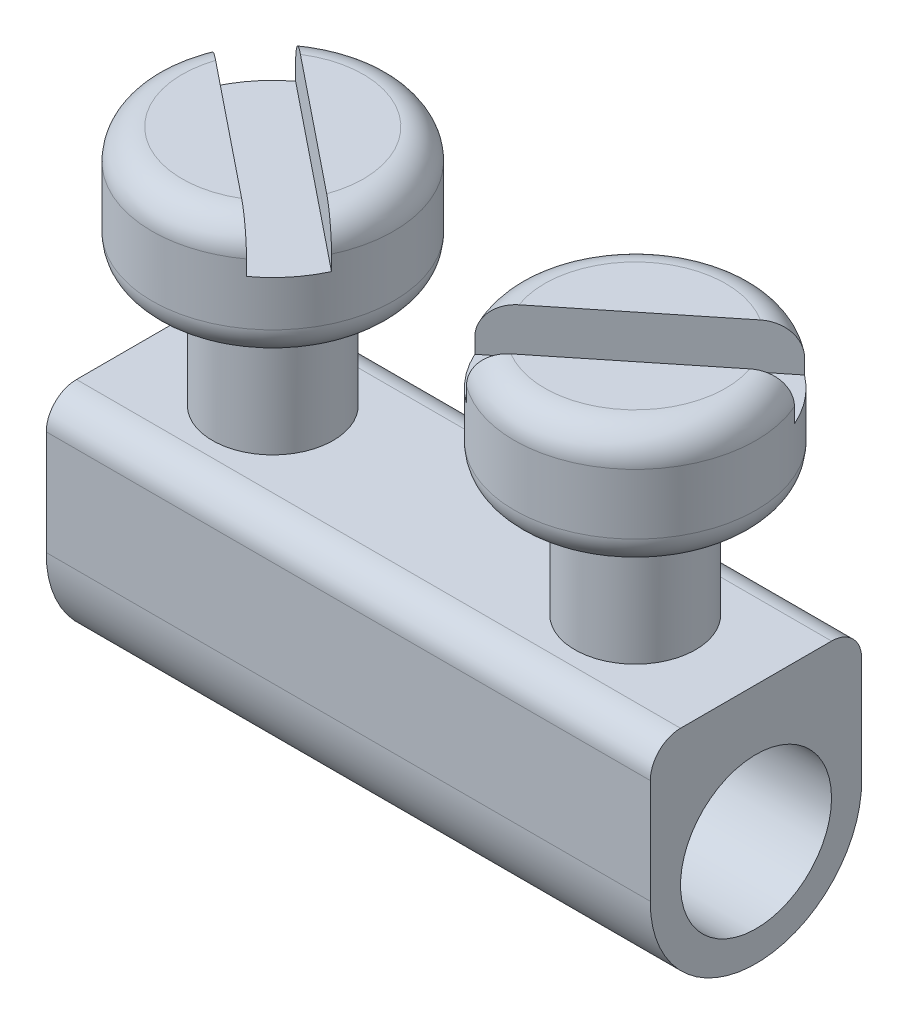
SolidWorks part; units mm, degrees
ref_plane "Front" through (0, 0, 0) normal (0, 0, 1) x (1, 0, 0)
ref_plane "Top" through (0, 0, 0) normal (0, 1, 0) x (1, 0, 0)
ref_plane "Right" through (0, 0, 0) normal (1, 0, 0) x (0, 0, -1)
sketch "Эскиз1" plane through (0, 0, 0) normal (1, 0, 0) x (0, 0, -1)
  line L0 (-5.8803, 0) -> (7.2033, 0) construction
  line L1 (0, 3.4363) -> (0, -3.473) construction
  line L2 (-1.75, 2.2026) -> (1.75, 2.2026)
  line L3 (-1.75, 2.2026) -> (-1.75, -0.0289)
  line L4 (1.75, 2.2026) -> (1.75, -0.0289)
  arc A0 (-1.75, -0.0289) -> (1.75, -0.0289) centre (0, -0.0473) ccw
  circle A1 centre (0, -0.0473) radius 1.25
  point P4 (0, 2.2026)
  point P12 (0, -1.7974)
  dimension "D2" = 1.7501
  dimension "D4" = 2.5
  dimension "D1" = 3.5
  dimension "D3" = 4
extrude "Бобышка-Вытянуть1" add sketch "Эскиз1" along normal mid plane 10
sketch "Эскиз2" plane through (0, 2.2026, 0) normal (0, 1, 0) x (1, 0, 0)
  line L0 (0, -4.2446) -> (0, 3.6659) construction
  line L1 (5, 1.75) -> (5, -1.75) construction
  circle A0 centre (3, 0) radius 1
  circle A1 centre (-3, 0) radius 1
  dimension "D1" = 2
  dimension "D2" = 2
extrude "Бобышка-Вытянуть8" add sketch "Эскиз2" along normal blind 4
extrude "Бобышка-Вытянуть9" add sketch "Эскиз2<2>" against normal blind 2
sketch "Эскиз2<2>" plane through (0, 2.2026, 0) normal (0, 1, 0) x (1, 0, 0) same geometry as "Эскиз2"
sketch "Эскиз4" plane through (0, 6.2026, 0) normal (0, 1, 0) x (1, 0, 0)
  line L0 (-4.2125, 1.5905) -> (-1.1859, -0.8421)
  line L1 (-4.8375, 0.8098) -> (-1.8108, -1.6227)
  line L2 (0, 2.5483) -> (0, -3.1773) construction
  line L3 (4.8375, 0.8098) -> (1.8108, -1.6227)
  line L4 (4.2125, 1.5905) -> (1.1859, -0.8421)
  circle A0 centre (-3, 0) radius 2
  circle A1 centre (-3, 0) radius 1 construction
  circle A4 centre (3, 0) radius 2
  circle M1 centre (-3, 0) radius 1
  dimension "D1" = 4
  dimension "D2" = 1
extrude "Бобышка-Вытянуть10" add sketch "Эскиз4" against normal blind 2 contours L0 A0 L1 M1 | L1 A0 M1 | L0 A0 M1 | L0 M1 | L1 L0 M1 | L1 M1 | L1 A0 L0 M1 | A4 L4 | A4 L3 L4 | A4 L3 region at (-2.2566, 6.2026, -0.9249) region at (-4.1565, 6.2026, -0.9028) region at (-2.5655, 6.2026, -0.5406) region at (-3.0113, 6.2026, 0.014) region at (-3.7534, 6.2026, 0.9374) region at (-1.8696, 6.2026, 0.9353) region at (-3.4489, 6.2026, 0.5585) region at (3.7116, 6.2026, 0.8854) region at (3.0122, 6.2026, 0.0152) region at (2.3024, 6.2026, -0.868)
extrude "Вырез-Вытянуть1" cut sketch "Эскиз4<3>" against normal blind 0.75 contours L1 L0 M1 | L0 A0 L1 M1 | L1 A0 L0 M1 | A4 L3 L4 region at (-4.1565, 6.2026, -0.9028) region at (-3.0113, 6.2026, 0.014) region at (-1.8696, 6.2026, 0.9353) region at (3.0122, 6.2026, 0.0152)
sketch "Эскиз4<3>" plane through (0, 6.2026, 0) normal (0, 1, 0) x (1, 0, 0) same geometry as "Эскиз4"
fillet "Скругление2" radius 0.5 8 edges at (0, 2.2026, 1.75) (0, 2.2026, -1.75) (-4.2529, 6.2026, 1.5589) (-1.7471, 6.2026, -1.5589) (-3, 4.2026, 2) (3, 4.2026, 2) (1.7471, 6.2026, -1.5589) (4.2529, 6.2026, 1.5589)
